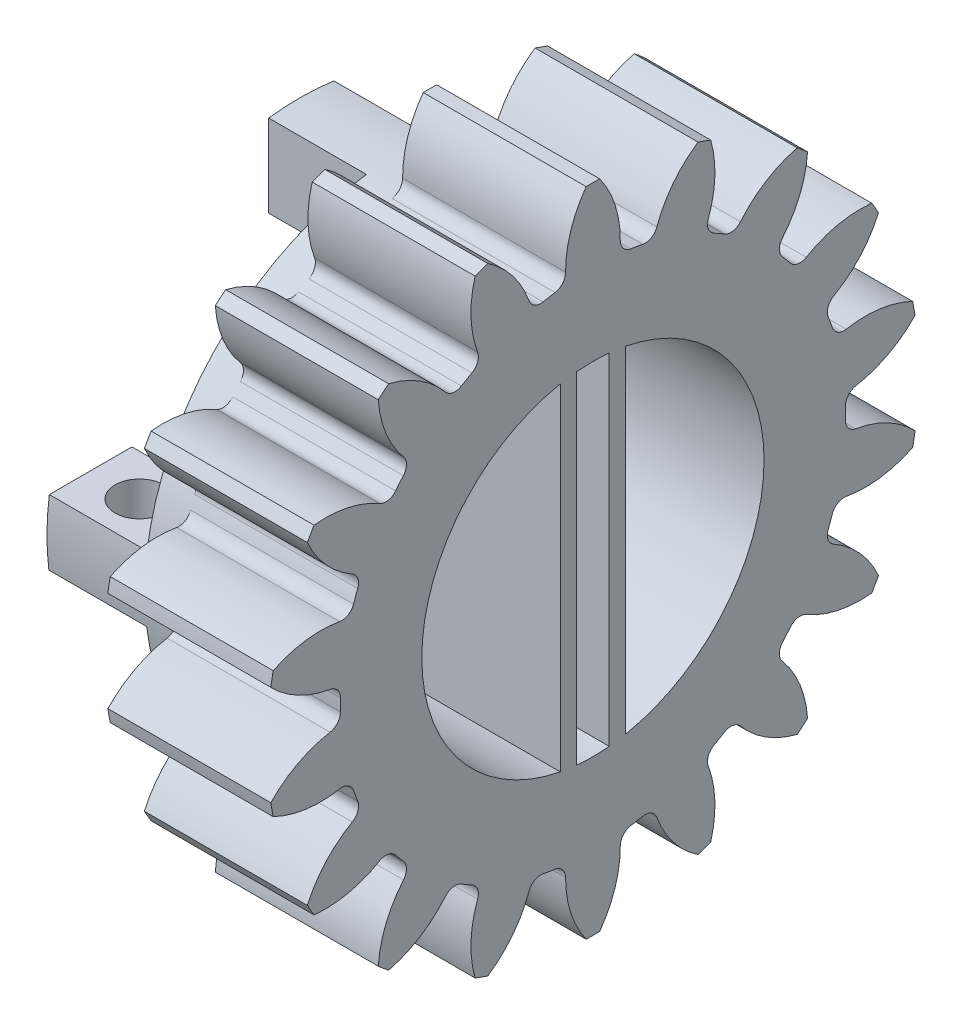
SolidWorks part; units mm, degrees
ref_plane "Front Plane" through (0, 0, 0) normal (1, 0, 0) x (0, 1, 0)
ref_plane "Top Plane" through (0, 0, 0) normal (0, 0, 1) x (0, 1, 0)
ref_plane "Right Plane" through (0, 0, 0) normal (0, 1, 0) x (-1, 0, 0)
sketch "Sketch1" plane through (0, 0, 0) normal (1, 0, 0) x (0, 1, 0)
  circle A0 centre (0, 0) radius 20
  dimension "D1" = 40
extrude "Boss-Extrude1" add sketch "Sketch1" along normal blind 10
sketch "Sketch2" plane through (10, 0, 0) normal (1, 0, 0) x (0, 1, 0)
  line L0 (0, 0) -> (0, 20) construction
  line L1 (0, 0) -> (-1.0595, 15.4638) construction
  line L2 (0, 14.2362) -> (-1.3642, 17.1618) construction
  arc A0 (1.0595, 15.4638) -> (-1.0595, 15.4638) centre (0, 0) ccw
  arc A1 (1.7182, 17.9178) -> (-1.7182, 17.9178) centre (0, 0) ccw construction
  arc A2 (3.0646, 19.7638) -> (-3.0646, 19.7638) centre (0, 0) ccw
  arc A3 (-1.0595, 15.4638) -> (-3.0646, 19.7638) centre (-7.6396, 15.0129) ccw
  arc A4 (1.0595, 15.4638) -> (3.0646, 19.7638) centre (7.6396, 15.0129) cw
  circle A5 centre (0, 0) radius 20 construction
  point P14 (-1.662, 17.8003)
  dimension "D1" = 40
  dimension "D2" = 36
  dimension "D3" = 4.5
  dimension "D4" = 25
  dimension "D5" = 3.4416
extrude "Cut-Extrude1" cut sketch "Sketch2" against normal through all
fillet "Fillet1" radius 0.76 2 edges at (5, 1.0595, 15.4638) (5, -1.0595, 15.4638)
pattern_circular "CirPattern1" count 18 over 360 about axis through (10, 0, 0) along (1, 0, 0) of "Cut-Extrude1", "Fillet1"
sketch "Sketch3" plane through (10, 0, 0) normal (1, 0, 0) x (0, 1, 0)
  line L0 (2, -1.5) -> (2, 1.5)
  arc A0 (2, 1.5) -> (2, -1.5) centre (0, 0) ccw
  dimension "D1" = 2.5
  dimension "D2" = 2
extrude "Cut-Extrude2" cut sketch "Sketch3" against normal through all
sketch "Sketch4" [suppressed] plane through (10, 0, 0) normal (1, 0, 0) x (0, 1, 0)
  line L0 (-32, 0) -> (32, 0)
  circle A0 centre (0, 0) radius 32 construction
  arc A1 (-32, 0) -> (32, 0) centre (0, 0) ccw
  point P7 (0, 0)
extrude "Cut-Extrude3" [suppressed] cut sketch "Sketch4" against normal through all
ref_plane "Plane1" [suppressed] through (0, 0, 2) normal (0, 0, -1) x (-1, 0, 0)
sketch "Sketch8" [suppressed] plane through (0, 0, 2) normal (0, 0, -1) x (-1, 0, 0)
  line L0 (-5, 32) -> (-5, -32) construction
  line L1 (0, 32) -> (-10, 32) construction
  line L2 (0, -32) -> (-10, -32) construction
  line L3 (0, 0) -> (-10, 0) construction
  line L4 (-3.3546, 5.15) -> (-1.7091, 8)
  line L5 (-1.7091, 8) -> (-3.3546, 10.85)
  line L6 (-3.3546, 10.85) -> (-6.6454, 10.85)
  line L7 (-6.6454, 10.85) -> (-8.2909, 8) construction
  line L8 (-8.2909, 8) -> (-6.6454, 5.15) construction
  line L9 (-6.6454, 5.15) -> (-3.3546, 5.15)
  line L10 (-10, 32) -> (-10, -32) construction
  line L11 (-6.6454, 5.15) -> (-10, 5.15)
  line L12 (-10, 5.15) -> (-10, 10.85)
  line L13 (-10, 10.85) -> (-6.6454, 10.85)
  line L14 (-8.2909, -8) -> (-6.6454, -5.15) construction
  line L15 (-6.6454, -10.85) -> (-8.2909, -8) construction
  line L16 (-10, -10.85) -> (-6.6454, -10.85)
  line L17 (-10, -5.15) -> (-10, -10.85)
  line L18 (-6.6454, -5.15) -> (-10, -5.15)
  line L19 (-6.6454, -5.15) -> (-3.3546, -5.15)
  line L20 (-3.3546, -10.85) -> (-6.6454, -10.85)
  line L21 (-1.7091, -8) -> (-3.3546, -10.85)
  line L22 (-3.3546, -5.15) -> (-1.7091, -8)
  circle A0 centre (-5, 8) radius 2.85 construction
  circle A1 centre (-5, -8) radius 2.85 construction
  dimension "D1" = 5.7
  dimension "D2" = 16
extrude "Cut-Extrude6" [suppressed] cut sketch "Sketch8" against normal blind 2.6
sketch "Sketch9" [suppressed] plane through (0, 0, 0) normal (0, 0, -1) x (1, 0, 0)
  line L0 (5, 32) -> (5, -32) construction
  line L1 (0, 32) -> (10, 32) construction
  line L2 (0, -32) -> (10, -32) construction
  line L3 (0, 0) -> (10, 0) construction
  line L4 (10, -32) -> (10, 32) construction
  line L5 (1.7091, 8) -> (3.3546, 5.15)
  line L6 (3.3546, 10.85) -> (1.7091, 8)
  line L7 (10, 10.85) -> (3.3546, 10.85)
  line L8 (10, 5.15) -> (10, 10.85)
  line L9 (3.3546, 5.15) -> (10, 5.15)
  line L10 (1.7091, 8) -> (3.3546, 5.15) construction
  line L11 (3.3546, 10.85) -> (1.7091, 8) construction
  line L12 (10, 10.85) -> (3.3546, 10.85) construction
  line L13 (10, 5.15) -> (10, 10.85) construction
  line L14 (3.3546, 5.15) -> (10, 5.15) construction
  line L15 (3.3546, -5.15) -> (10, -5.15) construction
  line L16 (10, -5.15) -> (10, -10.85) construction
  line L17 (10, -10.85) -> (3.3546, -10.85) construction
  line L18 (3.3546, -10.85) -> (1.7091, -8) construction
  line L19 (1.7091, -8) -> (3.3546, -5.15) construction
  circle A0 centre (5, 8) radius 1.75
  circle A1 centre (5, -8) radius 1.75
  dimension "D2" = 3.5
  dimension "D1" = 0
extrude "Cut-Extrude7" [suppressed] cut sketch "Sketch9" against normal blind 11
sketch "Sketch12" plane through (10, 0, 0) normal (1, 0, 0) x (0, 1, 0)
  circle A0 centre (0, 0) radius 10.5
  dimension "D1" = 21
extrude "Cut-Extrude8" cut sketch "Sketch12" against normal through all and the other way through all
sketch "Sketch17" plane through (0, 0, 0) normal (-1, 0, 0) x (0, -1, 0)
  circle A0 centre (0, 0) radius 8
  circle A2 centre (0, 0) radius 12.7
  dimension "D1" = 25.4
extrude "Boss-Extrude3" [suppressed] add sketch "Sketch17" along normal blind 1
sketch "Sketch22" plane through (0, 0, 0) normal (-1, 0, 0) x (0, -1, 0)
  circle A0 centre (0, 0) radius 15.5
  circle A1 centre (0, 0) radius 10.5 construction
  circle A2 centre (0, 0) radius 10.5
  arc A3 (-9.6758, 12.1091) -> (-10.2449, 11.6315) centre (0, 0) ccw construction
extrude "Boss-Extrude6" add sketch "Sketch22" along normal blind 2
sketch "Sketch18" plane through (-2, 0, 0) normal (-1, 0, 0) x (0, -1, 0)
  line L13 (-1.8958, -10.3274) -> (-1.8958, -15.3836)
  line L14 (2.1042, -10.287) -> (2.1042, -15.3565)
  line L15 (-10.3274, 1.8958) -> (-15.3836, 1.8958)
  line L16 (-10.287, -2.1042) -> (-15.3565, -2.1042)
  line L17 (1.8958, 10.3274) -> (1.8958, 15.3836)
  line L18 (-2.1042, 10.287) -> (-2.1042, 15.3565)
  line L19 (10.3274, -1.8958) -> (15.3836, -1.8958)
  line L20 (10.287, 2.1042) -> (15.3565, 2.1042)
  line L23 (0, -10.5) -> (0, -12.7) construction
  arc A12 (-1.8958, -15.3836) -> (2.1042, -15.3565) centre (0, 0) ccw
  arc A13 (-15.3836, 1.8958) -> (-15.3565, -2.1042) centre (0, 0) ccw
  arc A14 (-10.3274, 1.8958) -> (-10.287, -2.1042) centre (0, 0) ccw
  arc A15 (1.8958, 15.3836) -> (-2.1042, 15.3565) centre (0, 0) ccw
  arc A16 (1.8958, 10.3274) -> (-2.1042, 10.287) centre (0, 0) ccw
  arc A17 (15.3836, -1.8958) -> (15.3565, 2.1042) centre (0, 0) ccw
  arc A18 (10.3274, -1.8958) -> (10.287, 2.1042) centre (0, 0) ccw
  circle A19 centre (0, 0) radius 15.5 construction
  circle A22 centre (0, 0) radius 10.5 construction
  circle A23 centre (0, 0) radius 10.5 construction
  arc A25 (-1.8958, -10.3274) -> (2.1042, -10.287) centre (0, 0) ccw
  point P29 (0, 0)
  dimension "D1" = 4
  dimension "D2" = 4
extrude "Boss-Extrude4" add sketch "Sketch18" along normal blind 6
sketch "Sketch26" plane through (0, 2.1042, 0) normal (0, 1, 0) x (-1, 0, 0)
  line L0 (5, 12.8218) -> (5, 10.287) construction
  line L1 (8, -10.3274) -> (8, 10.287) construction
  line L2 (2, 15.3565) -> (2, 10.287) construction
  line L3 (8, -0.0202) -> (1.4708, -0.0202) construction
  line L4 (8, 15.3565) -> (8, 10.287) construction
  line L6 (8, 12.8218) -> (2, 12.8218) construction
  line L10 (8, 10.287) -> (2, 10.287) construction
  circle A0 centre (5, 12.8218) radius 1.5
  circle A1 centre (5, -12.8622) radius 1.5
  point P5 (0, 0)
  point P9 (0, 0)
  point P10 (0, 0)
  point P14 (0, 0)
  dimension "D1" = 3
extrude "Cut-Extrude17" cut sketch "Sketch26" against normal through all both and the other way through all
sketch "Sketch28" plane through (10, 0, 0) normal (1, 0, 0) x (0, 1, 0)
  line L0 (-10.5, 0) -> (10.5, 0) construction
  line L1 (-10.4523, -1) -> (10.4523, -1)
  line L2 (-10.5, -2) -> (10.5, -2) construction
  line L3 (-10.3078, -2) -> (10.3078, -2)
  line L4 (-10.5, -1) -> (10.5, -1) construction
  line L5 (-10.3078, 2) -> (10.3078, 2)
  line L6 (-10.4523, 1) -> (10.4523, 1)
  circle A0 centre (0, 0) radius 10.5 construction
  arc A1 (-10.4523, -1) -> (-10.3078, -2) centre (0, 0) ccw
  arc A2 (10.3078, -2) -> (10.4523, -1) centre (0, 0) ccw
  arc A3 (-10.4523, 1) -> (-10.3078, 2) centre (0, 0) cw
  arc A4 (10.3078, 2) -> (10.4523, 1) centre (0, 0) cw
  dimension "D1" = 1
  dimension "D3" = 1
extrude "Boss-Extrude7" add sketch "Sketch28" against normal up to surface (12 mm away) up to face at (-2, 8.3733, 8.2381)
sketch "Sketch30" plane through (-2, 0, 0) normal (-1, 0, 0) x (0, -1, 0)
  line L0 (-10.3078, 2) -> (10.3078, 2) construction
  line L1 (-7.2556, 2) -> (8.1376, 2)
  line L2 (-7.2556, 2) -> (-7.2556, 6.3938)
  line L3 (-7.2556, 6.3938) -> (8.1376, 6.3938)
  line L4 (8.1376, 2) -> (8.1376, 6.3938)
equation "\"No. of Teeth\"= 18"
equation "\"Module\"= 2"
equation "\"Bore Diameter\"= 5"
equation "\"Pressure Angle\"= 25"
equation "\"Outer Diameter\"= ( \"No. of Teeth\" + 2 ) * \"Module\""
equation "\"Pitch Diameter\"= ( \"No. of Teeth\" * \"Module\" )"
equation "\"Backlash\"= 0.15 * \"Module\""
equation "\"Arc Length\"= ( ( \"Module\" * pi ) / 2 ) + \"Backlash\""
equation "\"Filet Radius\"= 0.38 * \"Module\""
equation "\"Tooth Depth\" = IIF ( \"Module\" <= 1.25 , \"Module\" * 2.4 , \"Module\" * 2.25 )"
equation "\"D1@Fillet1\"=\"Filet Radius\""
equation "\"D1@CirPattern1\"=\"No. of Teeth\""
equation "\"D1@Sketch1\"=\"Outer Diameter\""
equation "\"D5@Sketch2\"=\"Arc Length\""
equation "\"D4@Sketch2\"=\"Pressure Angle\""
equation "\"D2@Sketch2\"=\"Pitch Diameter\""
equation "\"D1@Sketch2\"=\"Outer Diameter\""
equation "\"D3@Sketch2\"= \"Tooth Depth\""
